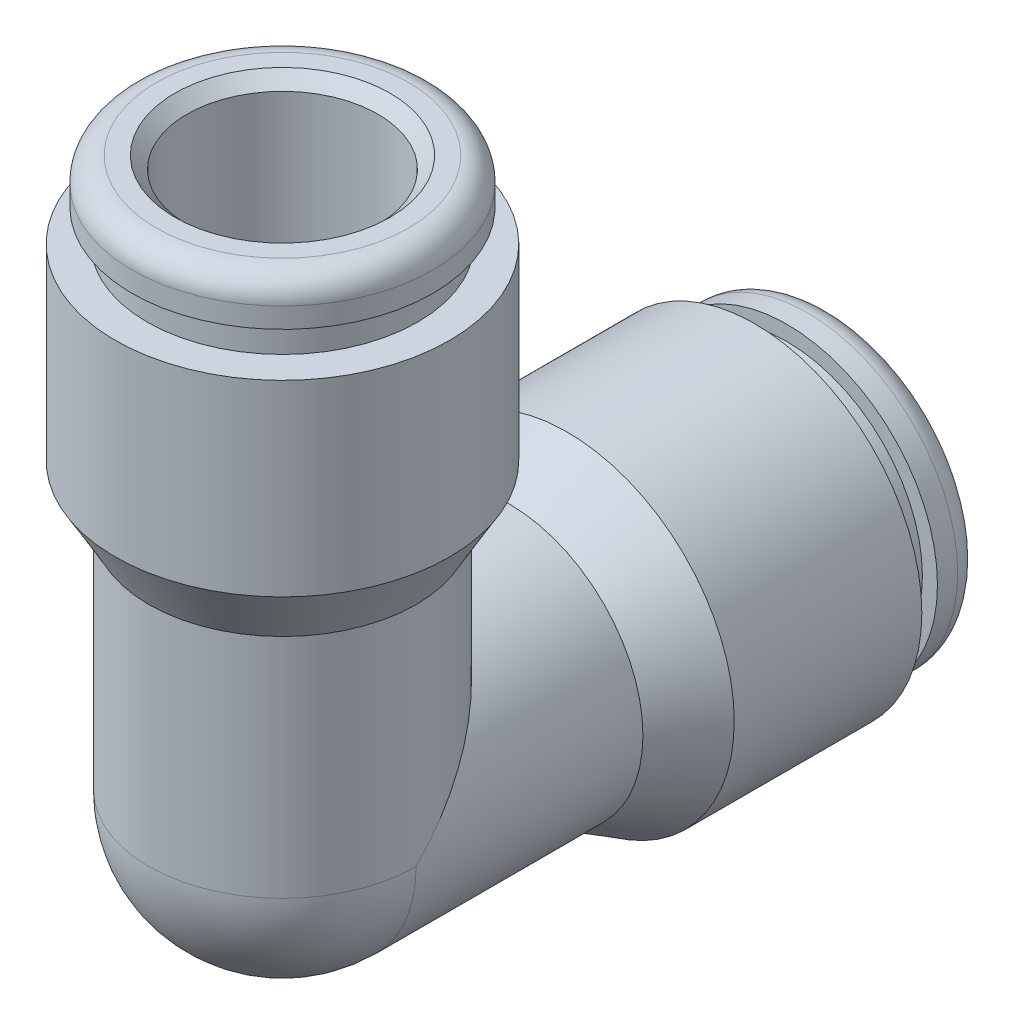
SolidWorks part; units mm, degrees
ref_plane "Front Plane" through (0, 0, 0) normal (0, 0, 1) x (1, 0, 0)
ref_plane "Top Plane" through (0, 0, 0) normal (0, 1, 0) x (1, 0, 0)
ref_plane "Right Plane" through (0, 0, 0) normal (1, 0, 0) x (0, 0, -1)
sketch "Sketch1" plane through (0, 0, 0) normal (1, 0, 0) x (0, 0, -1)
  line L0 (15.853, 4.725) -> (16.488, 4.725)
  line L1 (8.9437, 5.25) -> (14.837, 5.25)
  line L2 (0, 4.2) -> (0, 2.238)
  line L3 (6, 3) -> (16.869, 3)
  line L4 (17.25, 3.963) -> (17.25, 3.381)
  line L5 (0, 0) -> (0, 17.25) construction
  line L6 (14.837, 5.25) -> (14.837, 4.2525)
  line L7 (14.837, 4.2525) -> (15.853, 4.2525)
  line L8 (15.853, 4.725) -> (15.853, 4.2525)
  line L9 (-5.25, 17.25) -> (5.25, 17.25) construction
  line L10 (0, 0) -> (17.25, 0) construction
  line L11 (6, 3) -> (6, 2.238)
  line L12 (16.869, 3) -> (17.25, 3.381)
  line L13 (0, 0) -> (0, 2.238) construction
  line L14 (0, 4.2) -> (7.125, 4.2)
  line L15 (7.125, 4.2) -> (8.9437, 5.25)
  line L16 (6, 2.238) -> (0, 2.238)
  arc A0 (16.488, 4.725) -> (17.25, 3.963) centre (16.488, 3.963) cw
  point P1 (17.25, 3)
  point P20 (17.25, 4.725)
  dimension "D4" = 0.762
  dimension "tube od" = 6
  dimension "D1" = 1.397
  dimension "D2" = 1.016
  dimension "D3" = 8.505
  dimension "D6" = 9.45
  dimension "D9" = 30
  dimension "D10" = 8.4
  dimension "D5" = 10.125
  dimension "D8" = 10.5
  dimension "D11" = 0.762
revolve "Revolve1" add sketch "Sketch1" angle 360 about L10
ref_axis "Axis1" through (-5.775, 0, 0) along (1, 0, 0)
pattern_circular "CirPattern1" count 2 over 90 about axis through (-5.775, 0, 0) along (1, 0, 0) of bodies 118 123
sketch "Sketch2" plane through (0, 0, 0) normal (0, 0, 1) x (1, 0, 0)
  line L0 (-4.2, 0) -> (-2.238, 0)
  line L1 (-4.2, 0) -> (4.2, 0) construction
  line L2 (2.238, 0) -> (4.2, 0)
  arc A0 (-4.2, 0) -> (4.2, 0) centre (0, 0) ccw
  arc A2 (-2.238, 0) -> (2.238, 0) centre (0, 0) ccw
  circle A4 centre (0, 0) radius 2.238 construction
  circle A5 centre (0, 0) radius 4.2 construction
revolve "Revolve2" add sketch "Sketch2" angle 90 about L1 reverse direction yes
combine bodies "Combine1" operation type add bodies to combine 122 124
sketch "Sketch3" plane through (0, 0, 0) normal (1, 0, 0) x (0, 0, -1)
  line L0 (17.25, 3.381) -> (16.869, 3)
  line L1 (16.869, 3) -> (6, 3)
  line L2 (6, 3) -> (6, 2.238)
  line L3 (6, 2.238) -> (0, 2.238)
  line L4 (0, 2.238) -> (0, 0)
  line L5 (0, 0) -> (17.25, 0)
  line L6 (17.25, 0) -> (17.25, 3.381)
revolve "Cut-Revolve1" cut sketch "Sketch3" angle 360 about L5
pattern_circular "CirPattern2" count 2 over 90 about axis through (-5.775, 0, 0) along (1, 0, 0) of "Cut-Revolve1"
equation "\"D6@Sketch1\" = \"G@Sketch1\"*.9"
equation "\"D3@Sketch1\" = \"D6@Sketch1\"*.9"
equation "\"D10@Sketch1\" = \"G@Sketch1\"*.8"
equation "\"D5@Sketch1\" = \"L@Sketch1\"*.45"
equation "\"D8@Sketch1\" = \"G@Sketch1\""
